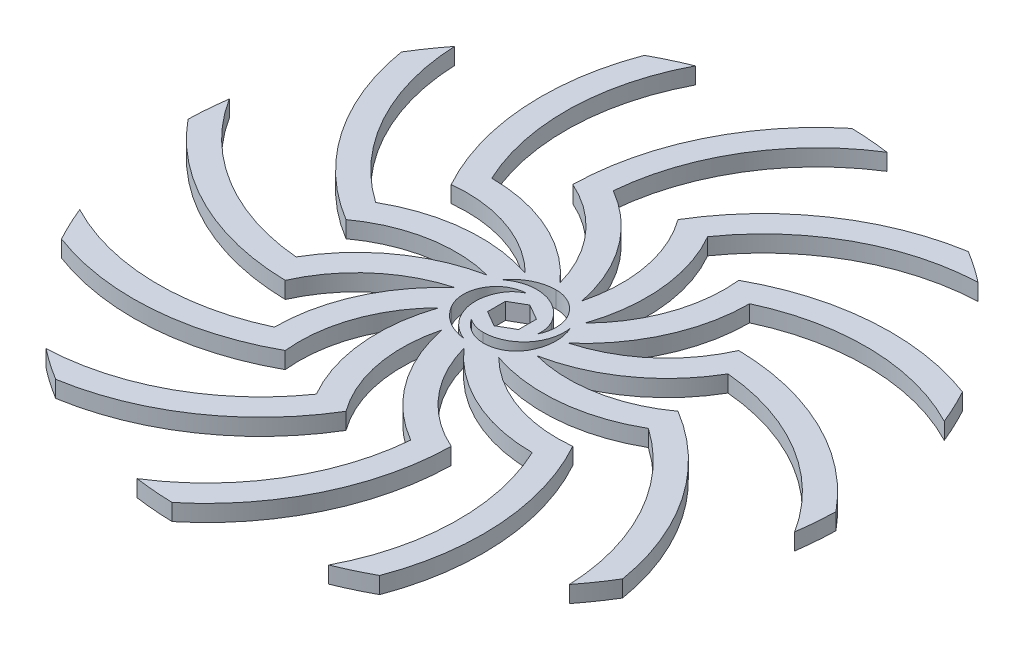
SolidWorks part; units mm, degrees
ref_plane "Front Plane" through (0, 0, 0) normal (0, 0, 1) x (1, 0, 0)
ref_plane "Top Plane" through (0, 0, 0) normal (0, 1, 0) x (1, 0, 0)
ref_plane "Right Plane" through (0, 0, 0) normal (1, 0, 0) x (0, 0, -1)
sketch "Sketch1" plane through (0, 0, 0) normal (0, 1, 0) x (1, 0, 0)
  line L0 (0, 0) -> (3.5728, 0)
  line L1 (0, 0) -> (0, 40) construction
  circle A0 centre (0, 0) radius 40
  circle A1 centre (0, 0) radius 42
  arc A2 (0, 0) -> (0, 20) centre (-13.7477, 10) ccw
  arc A3 (3.5728, 0) -> (3.5728, 20) centre (-13.7477, 10) ccw
  arc A4 (0, 20) -> (20.8254, 34.1512) centre (25.7173, 4.5527) cw
  arc A5 (3.5728, 20) -> (24.614, 31.5301) centre (25.7173, 4.5527) cw
  point P9 (0, 0)
  point P13 (0, 20)
  dimension "D1" = 80
  dimension "D2" = 84
  dimension "D3" = 17
  dimension "D4" = 20
  dimension "D5" = 30
  dimension "D6" = 27
extrude "Boss-Extrude1" add sketch "Sketch1" along normal blind 2 contours A3 A5 A0 A4 A2 L0 region at (3.6732, 0, -10)
ref_axis "Axis1" through (0, 0, 0) along (0, 1, 0)
pattern_circular "CirPattern1" count 12 over 360 about axis through (0, 0, 0) along (0, 1, 0) of bodies 101
sketch "Sketch2" plane through (0, 0, 0) normal (0, 1, 0) x (1, 0, 0)
  arc A0 (0, 0) -> (20, 0) centre (10, 13.7477) ccw construction
  arc A1 (1.7864, -3.0941) -> (19.1069, 6.9059) centre (1.7864, 16.9059) ccw construction
  arc A2 (0, 0) -> (20, 0) centre (10, 13.7477) ccw
  arc A3 (1.7864, -3.0941) -> (19.1069, 6.9059) centre (1.7864, 16.9059) ccw
  circle A4 centre (0, 0) radius 6.3246
  point P7 (5.7174, -2.704)
  point P8 (0, 0)
  point P9 (0, 0)
extrude "Boss-Extrude2" add sketch "Sketch2" along normal up to surface (2 mm away) contours A4 region at (5.9964, 0, 1.3465) up to face at (-20.5854, 2, 1.1757)
sketch "Sketch3" plane through (0, 2, 0) normal (0, 1, 0) x (1, 0, 0)
  line L0 (0, 0) -> (0, 1.4123) construction
  arc A0 (-2.1651, 1.25) -> (4.6112, -2.6623) centre (1.2231, -0.7061) ccw
  circle A1 centre (0, 0) radius 6.3246
  circle A2 centre (0, 0) radius 6.3246
  arc A3 (-3.0311, 1.75) -> (-0.5188, -5.2992) centre (1.2231, -0.7061) ccw
  circle A4 centre (0, 0) radius 5.3246
  circle A5 centre (0, 0) radius 2.5
  arc A6 (0, -2.5) -> (0, 5.3246) centre (0, 1.4123) ccw
  circle A7 centre (0, 0) radius 3.5
  arc A8 (0, -3.5) -> (4.8487, 2.2003) centre (0, 1.4123) ccw
  arc A9 (2.1651, 1.25) -> (-4.6112, -2.6623) centre (-1.2231, -0.7061) ccw
  arc A10 (3.0311, 1.75) -> (-4.3299, 3.0989) centre (-1.2231, -0.7061) ccw
  point P7 (0, 0)
  point P13 (0, 0)
  dimension "D3" = 5
  dimension "D4" = 7
  dimension "D1" = 0
  dimension "D2" = 1
  dimension "D5" = 3
extrude "Cut-Extrude1" cut sketch "Sketch3" against normal through all contours A7 A9 A4 A3 | A10 A7 A6 A4 | A8 A7 A0 A4 region at (2.7046, 2, 2.7563) region at (-3.7394, 2, 0.9641) region at (1.0347, 2, -3.7204)
scale "Scale1" scale about centroid uniform scaling yes scale factor 3.4
sketch "Sketch4" plane through (0, 4.4, 0) normal (0, 1, 0) x (1, 0, 0)
  line L1 (0, 7.3323) -> (-6.35, 3.6662)
  line L2 (-6.35, 3.6662) -> (-6.35, -3.6662)
  line L3 (-6.35, -3.6662) -> (0, -7.3323)
  line L4 (0, -7.3323) -> (6.35, -3.6662)
  line L5 (6.35, -3.6662) -> (6.35, 3.6662)
  line L6 (6.35, 3.6662) -> (0, 7.3323)
  circle A0 centre (0, 0) radius 6.35 construction
  point P1 (0, 0)
  point P10 (0, 0)
  dimension "D1" = 12.7
extrude "Cut-Extrude2" cut sketch "Sketch4" against normal up to surface (6.8 mm away) up to face at (7.8986, -2.4, 8.4784)
